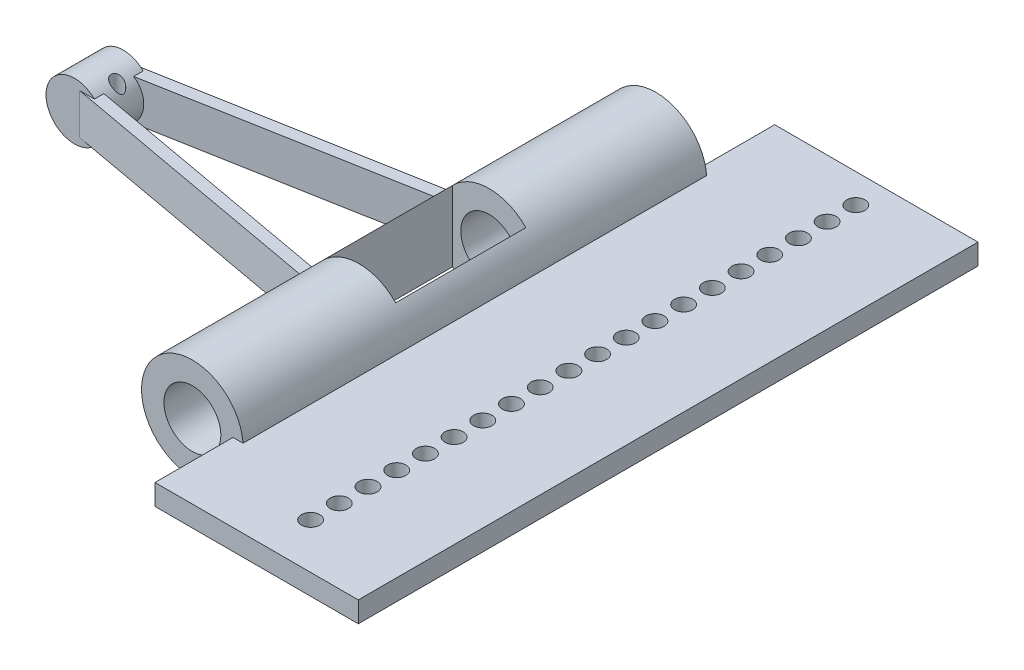
SolidWorks part; units mm, degrees
material "Gray Cast Iron"
ref_plane "Front Plane" through (0, 0, 0) normal (0, 0, 1) x (1, 0, 0)
ref_plane "Top Plane" through (0, 0, 0) normal (0, 1, 0) x (1, 0, 0)
ref_plane "Right Plane" through (0, 0, 0) normal (1, 0, 0) x (0, 0, -1)
sketch "Sketch1" plane through (0, 0, 0) normal (0, 0, 1) x (1, 0, 0)
  circle A0 centre (0, 7) radius 12.5
  dimension "D2" = 25
  dimension "D1" = 7
extrude "Boss-Extrude1" add sketch "Sketch1" along normal mid plane 114
sketch "Sketch2" plane through (0, 0, 0) normal (0, 0, 1) x (1, 0, 0)
  circle A0 centre (0, 7) radius 7
  dimension "D2" = 14
  dimension "D1" = 7
extrude "Cut-Extrude1" cut sketch "Sketch2" against normal mid plane 120
sketch "Sketch3" plane through (0, 0, 0) normal (0, 1, 0) x (1, 0, 0)
  line L0 (-9, -16) -> (9, -16)
  line L1 (9, -16) -> (9, 16)
  line L2 (9, 16) -> (-9, 16)
  line L3 (-9, 16) -> (-9, -16)
  dimension "D1" = 18
  dimension "D2" = 32
  dimension "D3" = 9
  dimension "D4" = 16
extrude "Cut-Extrude2" cut sketch "Sketch3" against normal mid plane 60
sketch "Sketch4" plane through (0, 0, 0) normal (0, 1, 0) x (1, 0, 0)
  line L0 (10, -76.2) -> (60, -76.2)
  line L1 (60, -76.2) -> (60, 76.2)
  line L2 (60, 76.2) -> (10, 76.2)
  line L3 (10, 76.2) -> (10, -76.2)
  circle A0 centre (37.1, 69.05) radius 2.25
  circle A1 centre (37.1, 61.9935) radius 2.25
  circle A2 centre (37.1, 54.937) radius 2.25
  circle A3 centre (37.1, 47.8805) radius 2.25
  circle A4 centre (37.1, 40.824) radius 2.25
  circle A5 centre (37.1, 33.7675) radius 2.25
  circle A6 centre (37.1, 26.711) radius 2.25
  circle A7 centre (37.1, 19.6545) radius 2.25
  circle A8 centre (37.1, 12.598) radius 2.25
  circle A9 centre (37.1, 5.5415) radius 2.25
  circle A10 centre (37.1, -1.515) radius 2.25
  circle A11 centre (37.1, -8.5715) radius 2.25
  circle A12 centre (37.1, -15.628) radius 2.25
  circle A13 centre (37.1, -22.6845) radius 2.25
  circle A14 centre (37.1, -29.741) radius 2.25
  circle A15 centre (37.1, -36.7975) radius 2.25
  circle A16 centre (37.1, -43.854) radius 2.25
  circle A17 centre (37.1, -50.9105) radius 2.25
  circle A18 centre (37.1, -57.967) radius 2.25
  circle A19 centre (37.1, -65.0235) radius 2.25
  dimension "D3" = 4.5
  dimension "D6" = 4.5
  dimension "D9" = 4.5
  dimension "D12" = 4.5
  dimension "D15" = 4.5
  dimension "D18" = 4.5
  dimension "D21" = 4.5
  dimension "D24" = 4.5
  dimension "D27" = 4.5
  dimension "D30" = 4.5
  dimension "D33" = 4.5
  dimension "D36" = 4.5
  dimension "D39" = 4.5
  dimension "D42" = 4.5
  dimension "D45" = 4.5
  dimension "D48" = 4.5
  dimension "D51" = 4.5
  dimension "D54" = 4.5
  dimension "D57" = 4.5
  dimension "D60" = 4.5
  dimension "D1" = 37.1
  dimension "D2" = 69.05
  dimension "D4" = 37.1
  dimension "D5" = 61.9935
  dimension "D7" = 37.1
  dimension "D8" = 54.937
  dimension "D10" = 37.1
  dimension "D11" = 47.8805
  dimension "D13" = 37.1
  dimension "D14" = 40.824
  dimension "D16" = 37.1
  dimension "D17" = 33.7675
  dimension "D19" = 37.1
  dimension "D20" = 26.711
  dimension "D22" = 37.1
  dimension "D23" = 19.6545
  dimension "D25" = 37.1
  dimension "D26" = 12.598
  dimension "D28" = 37.1
  dimension "D29" = 5.5415
  dimension "D31" = 37.1
  dimension "D32" = 1.515
  dimension "D34" = 37.1
  dimension "D35" = 8.5715
  dimension "D37" = 37.1
  dimension "D38" = 15.628
  dimension "D40" = 37.1
  dimension "D41" = 22.6845
  dimension "D43" = 37.1
  dimension "D44" = 29.741
  dimension "D46" = 37.1
  dimension "D47" = 36.7975
  dimension "D49" = 37.1
  dimension "D50" = 43.854
  dimension "D52" = 37.1
  dimension "D53" = 50.9105
  dimension "D55" = 37.1
  dimension "D56" = 57.967
  dimension "D58" = 37.1
  dimension "D59" = 65.0235
  dimension "D61" = 50
  dimension "D62" = 152.4
  dimension "D63" = 10
  dimension "D64" = 76.2
extrude "Boss-Extrude2" add sketch "Sketch4" along normal blind 5.1 from offset 2.9
sketch "Sketch5" plane through (0, 0, 0) normal (0, 1, 0) x (1, 0, 0)
  line L0 (-9, 15.68) -> (-9, 18.68)
  line L1 (-9, 18.68) -> (-80, 5.77)
  line L2 (-80, 5.77) -> (-80, 2.77)
  line L3 (-80, 2.77) -> (-9, 15.68)
  line L4 (-9, -15.68) -> (-9, -18.68)
  line L5 (-9, -18.68) -> (-80, -5.77)
  line L6 (-80, -5.77) -> (-80, -2.77)
  line L7 (-80, -2.77) -> (-9, -15.68)
  dimension "D1" = 9
  dimension "D2" = 15.68
  dimension "D3" = 3
  dimension "D4" = 71
  dimension "D5" = 12.91
  dimension "D6" = 3
  dimension "D7" = 9
  dimension "D8" = 15.68
  dimension "D9" = 3
  dimension "D10" = 71
  dimension "D11" = 12.91
  dimension "D12" = 3
extrude "Boss-Extrude3" add sketch "Sketch5" along normal blind 10 from offset 2
sketch "Sketch6" plane through (0, 0, 0) normal (0, 0, 1) x (1, 0, 0)
  circle A0 centre (-80, 7) radius 7
  dimension "D3" = 14
  dimension "D1" = 80
  dimension "D2" = 7
extrude "Boss-Extrude4" add sketch "Sketch6" along normal mid plane 12
sketch "Sketch7" plane through (0, 0, 0) normal (0, 1, 0) x (1, 0, 0)
  circle A0 centre (-75.5, 0) radius 1.5
  dimension "D2" = 3
  dimension "D1" = 75.5
extrude "Cut-Extrude3" cut sketch "Sketch7" against normal mid plane 28
ref_axis "Axis1" through (0, 0, -83.82) along (0, 0, 1)
ref_plane "Plane1" through (-75.5, 0, 0) normal (1, 0, 0) x (0, 0, -1)
ref_axis "Axis2" through (-75.5, 0, -83.82) along (0, 0, 1)
